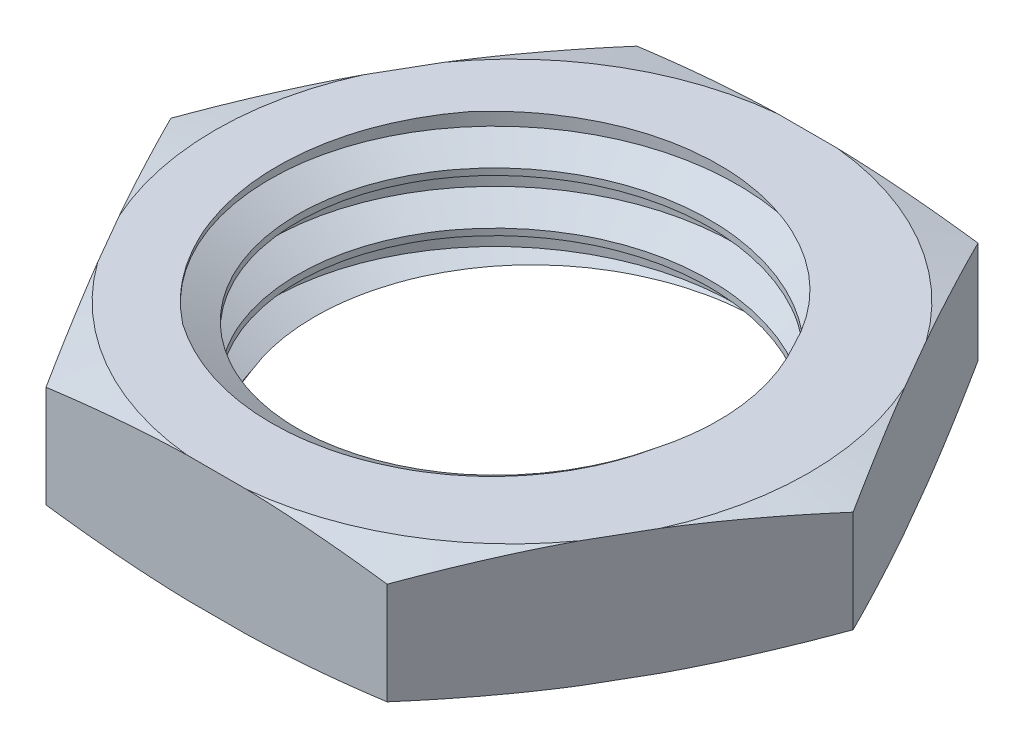
SolidWorks part; units mm, degrees
material "Brass"
ref_plane "Ön Düzlem" through (0, 0, 0) normal (0, 0, 1) x (1, 0, 0)
ref_plane "Üst Düzlem" through (0, 0, 0) normal (0, 1, 0) x (1, 0, 0)
ref_plane "Sağ Düzlem" through (0, 0, 0) normal (1, 0, 0) x (0, 0, -1)
sketch "Sketch1" plane through (0, 0, 0) normal (0, 1, 0) x (1, 0, 0)
  line L1 (-4.6188, 0) -> (-2.3094, -4)
  line L2 (-2.3094, -4) -> (2.3094, -4)
  line L3 (2.3094, -4) -> (4.6188, 0)
  line L4 (4.6188, 0) -> (2.3094, 4)
  line L5 (2.3094, 4) -> (-2.3094, 4)
  line L6 (-2.3094, 4) -> (-4.6188, 0)
  circle A0 centre (0, 0) radius 4 construction
  circle A1 centre (0, 0) radius 2.793
  dimension "D2" = 5.586
  dimension "D1" = 8
extrude "Boss-Extrude1" add sketch "Sketch1" along normal mid plane 1.7
sketch "Sketch6" plane through (0, 0.85, 0) normal (0, 1, 0) x (1, 0, 0)
  circle A0 centre (0, 0) radius 4.02
  dimension "D1" = 8.04
extrude "Cut-Extrude5" cut sketch "Sketch6" against normal blind 1.7 draft 75 flip side to cut
mirror "Mirror1" about plane through (0, 0, 0) normal (0, 1, 0) of "Cut-Extrude5"
thread "Thread1" pitch 0.7056 method cut profile "Thread Profile1" start angle 0, offset 1, length 0, pitch 0.7056, diameter 5.586
ref_plane "Plane1" through (-2.793, 1.85, 0) normal (0, 0, -1) x (1, 0, 0)
sketch "Thread Profile1" plane through (-2.793, 1.85, 0) normal (0, 0, -1) x (1, 0, 0)
  line L0 (0, 0) -> (0, 0.7056) construction
  line L11 (0, 0) -> (0, 0.6174)
  line L12 (0, 0.6174) -> (-0.3819, 0.3969)
  line L13 (-0.3819, 0.3969) -> (-0.3819, 0.2205)
  line L15 (-0.3819, 0.2205) -> (0, 0)
  line L17 (-0.3819, 0.3087) -> (0, 0.3087) construction
  point P2 (0, 0)
  dimension "Pitch" = 0.7056
  dimension "Profile_Angle" = 60
  dimension "Profile_Land" = 0.1764
  dimension "Profile_Height" = 0.3819
